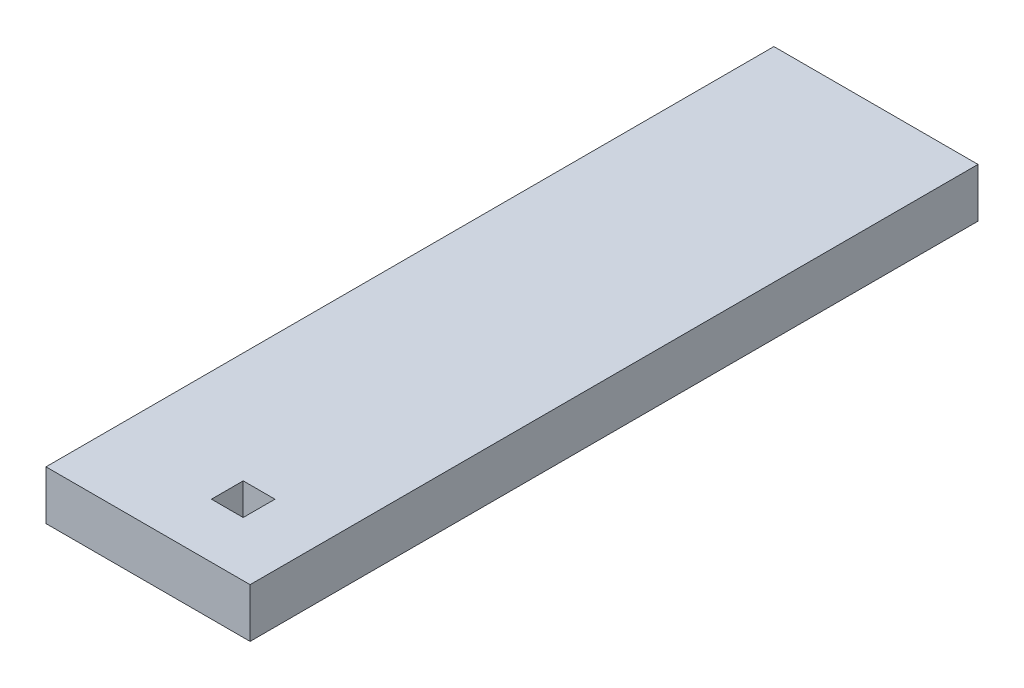
SolidWorks part; units mm, degrees
material "Acrylic (Medium-high impact)"
ref_plane "Front Plane" through (0, 0, 0) normal (0, 0, 1) x (1, 0, 0)
ref_plane "Top Plane" through (0, 0, 0) normal (0, 1, 0) x (1, 0, 0)
ref_plane "Right Plane" through (0, 0, 0) normal (1, 0, 0) x (0, 0, -1)
sketch "Sketch1" plane through (0, 0, 0) normal (0, 1, 0) x (1, 0, 0)
  line L0 (0, -18.9392) -> (0, 0) construction
  line L1 (5, -23.495) -> (-5, -23.495)
  line L2 (5, -23.495) -> (5, 23.495)
  line L3 (5, 23.495) -> (-5, 23.495)
  line L4 (-5, -23.495) -> (-5, 23.495)
  line L5 (5, -23.495) -> (-5, 23.495) construction
  line L6 (5, 23.495) -> (-5, -23.495) construction
  line L7 (-1.025, -17.9142) -> (1.025, -17.9142)
  line L8 (-1.025, -17.9142) -> (-1.025, -19.9642)
  line L9 (-1.025, -19.9642) -> (1.025, -19.9642)
  line L10 (1.025, -17.9142) -> (1.025, -19.9642)
  line L11 (-1.025, -17.9142) -> (1.025, -19.9642) construction
  line L12 (-1.025, -19.9642) -> (1.025, -17.9142) construction
  point P0 (0, 0)
  point P6 (0, -18.9392)
  dimension "D1" = 10
  dimension "D2" = 46.99
  dimension "D3" = 2.05
  dimension "D4" = 3.5308
extrude "Boss-Extrude1" add sketch "Sketch1" along normal blind 3.175 contours L1 L2 L3 L4 L7 L10 L9 L8 | L4 region at (0, 0, -0.1709)
sketch "Sketch2" plane through (0, 3.175, 0) normal (0, 1, 0) x (1, 0, 0)
  line L5 (5, -23.495) -> (-5, -23.495) construction
  line L6 (-5, 23.495) -> (-8.175, 23.495)
  line L7 (-5, 23.495) -> (-5, -23.495)
  line L8 (-5, -23.495) -> (-8.175, -23.495)
  line L9 (-8.175, 23.495) -> (-8.175, -23.495)
  dimension "D1" = 3.175
extrude "Boss-Extrude2" add sketch "Sketch2" against normal up to surface (3.175 mm away) up to face at (0, 0, 0)
equation "\"bottomThickness\"= .220in"
equation "\"wallThickness\"= .125in"
equation "\"D1@Boss-Extrude1\"=\"wallThickness\""
equation "\"D1@Sketch2\"=\"wallThickness\""
